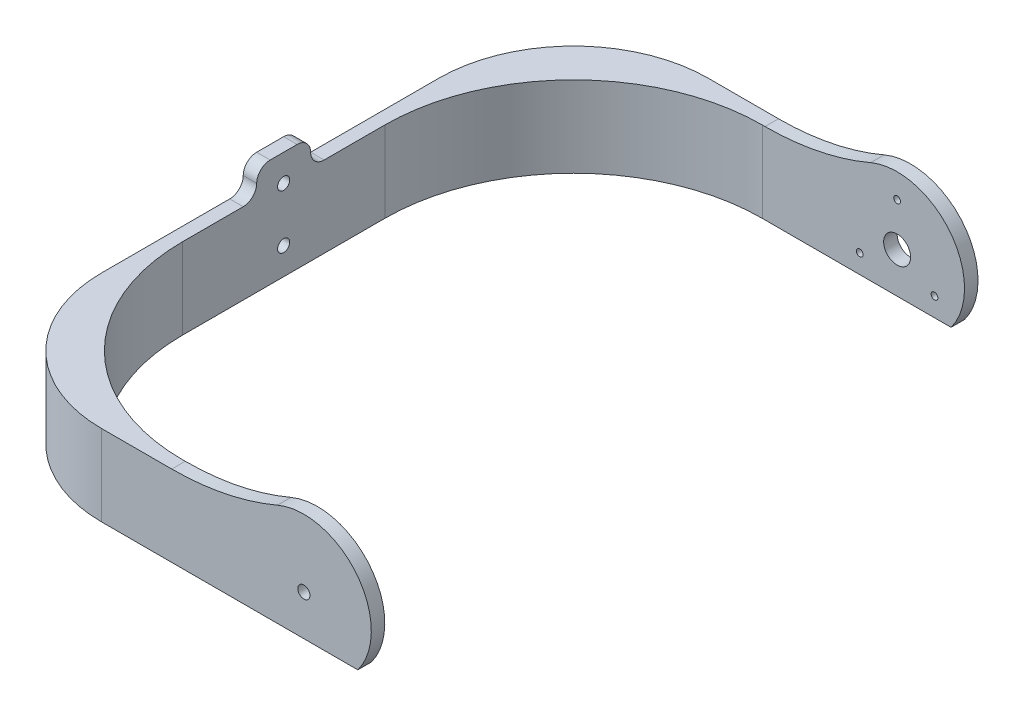
SolidWorks part; units mm, degrees
material "Polylactic Acid (PLA)"
ref_plane "Front Plane" through (0, 0, 0) normal (0, 0, 1) x (1, 0, 0)
ref_plane "Top Plane" through (0, 0, 0) normal (0, 1, 0) x (1, 0, 0)
ref_plane "Right Plane" through (0, 0, 0) normal (1, 0, 0) x (0, 0, -1)
sketch "Sketch1" plane through (0, 0, 0) normal (0, 0, 1) x (1, 0, 0)
  line L1 (0, 0) -> (125, 0)
  line L2 (0, 0) -> (0, 30)
  line L3 (0, 30) -> (125, 30)
  line L4 (125, 0) -> (125, 30)
  dimension "D1" = 125
  dimension "D2" = 30
extrude "Boss-Extrude1" add sketch "Sketch1" along normal mid plane 225
sketch "Sketch2" plane through (0, 0, 0) normal (0, 0, 1) x (1, 0, 0)
  line L0 (125, 0) -> (125, 30) construction
  line L2 (105, 0) -> (145, 0)
  line L4 (0, 0) -> (125, 0) construction
  arc A0 (145, 0) -> (105, 0) centre (125, 15) ccw
  dimension "D2" = 25
  dimension "D3" = 0
extrude "Boss-Extrude2" add sketch "Sketch2" along normal mid plane 225
sketch "Sketch4" plane through (0, 0, 0) normal (1, 0, 0) x (0, 0, -1)
  line L0 (112.5, 30) -> (112.5, 0) construction
  line L1 (-107.5, 55.7624) -> (107.5, 55.7624)
  line L2 (-107.5, 55.7624) -> (-107.5, -3.9412)
  line L3 (-107.5, -3.9412) -> (107.5, -3.9412)
  line L4 (107.5, 55.7624) -> (107.5, -3.9412)
  line L5 (-112.5, 30) -> (-112.5, 0) construction
  dimension "D1" = 5
  dimension "D2" = 5
extrude "Cut-Extrude2" cut sketch "Sketch4" along normal blind 160 from offset 5
ref_axis "Axis1" through (125, 15, -107.5) along (0, 0, -1)
sketch "Sketch5" plane through (0, 0, -112.5) normal (0, 0, -1) x (-1, 0, 0)
  line L0 (0, 0) -> (-145, 0) construction
  line L1 (-125, 15) -> (-138.8564, 7) construction
  line L2 (-125, 15) -> (-125, 31) construction
  circle A0 centre (-138.8564, 7) radius 1.25
  circle A1 centre (-125, 31) radius 1.25
  circle A2 centre (-111.1436, 7) radius 1.25
  circle A3 centre (-125.0041, 15) radius 5
  point P12 (-105, -4)
  point P13 (-105, -4)
  dimension "D1" = 2.5
  dimension "D4" = 10
  dimension "D2" = 3
  dimension "D3" = 120
  dimension "D5" = 16
  dimension "D6" = 7
extrude "Cut-Extrude3" cut sketch "Sketch5" against normal blind 10
fillet "Fillet1" radius 100 2 edges at (105, 30, 110) (105, 30, -110)
fillet "Fillet2" radius 70 2 edges at (5, 15, -107.5) (5, 15, 107.5)
fillet "Fillet3" radius 50 2 edges at (0, 15, -112.5) (0, 15, 112.5)
sketch "Sketch7" plane through (0, 0, 0) normal (-1, 0, 0) x (0, 0, 1)
  line L0 (62.5, 30) -> (-62.5, 30) construction
  line L1 (-10, 40) -> (10, 40)
  line L2 (-10, 40) -> (-10, 30)
  line L3 (-10, 30) -> (10, 30)
  line L4 (10, 40) -> (10, 30)
  line L6 (0, -22) -> (0, 22) construction
  dimension "D1" = 10
  dimension "D2" = 10
  dimension "D3" = 10
extrude "Boss-Extrude3" add sketch "Sketch7" against normal up to surface (5 mm away) up to face at (5, 15, 0)
sketch "Sketch6" plane through (0, 0, 0) normal (-1, 0, 0) x (0, 0, 1)
  line L0 (0, -22) -> (0, 22) construction
  line L1 (82.5, 0) -> (-82.5, 0) construction
  circle A0 centre (0, 10) radius 2.25
  circle A1 centre (0, 30) radius 2.25
  dimension "D1" = 4.5
  dimension "D3" = 10
  dimension "D2" = 2
extrude "Cut-Extrude4" cut sketch "Sketch6" against normal blind 10
fillet "Fillet4" radius 5 2 edges at (2.5, 30, -10) (2.5, 30, 10)
fillet "Fillet5" radius 5 2 edges at (2.5, 40, 10) (2.5, 40, -10)
sketch "Sketch8" plane through (0, 0, 107.5) normal (0, 0, -1) x (-1, 0, 0)
  circle A0 centre (-125, 15) radius 2.25
  dimension "D1" = 4.5
extrude "Cut-Extrude5" cut sketch "Sketch8" against normal up to surface (5 mm away) up to face at (90.2376, 21.4894, 112.5)
